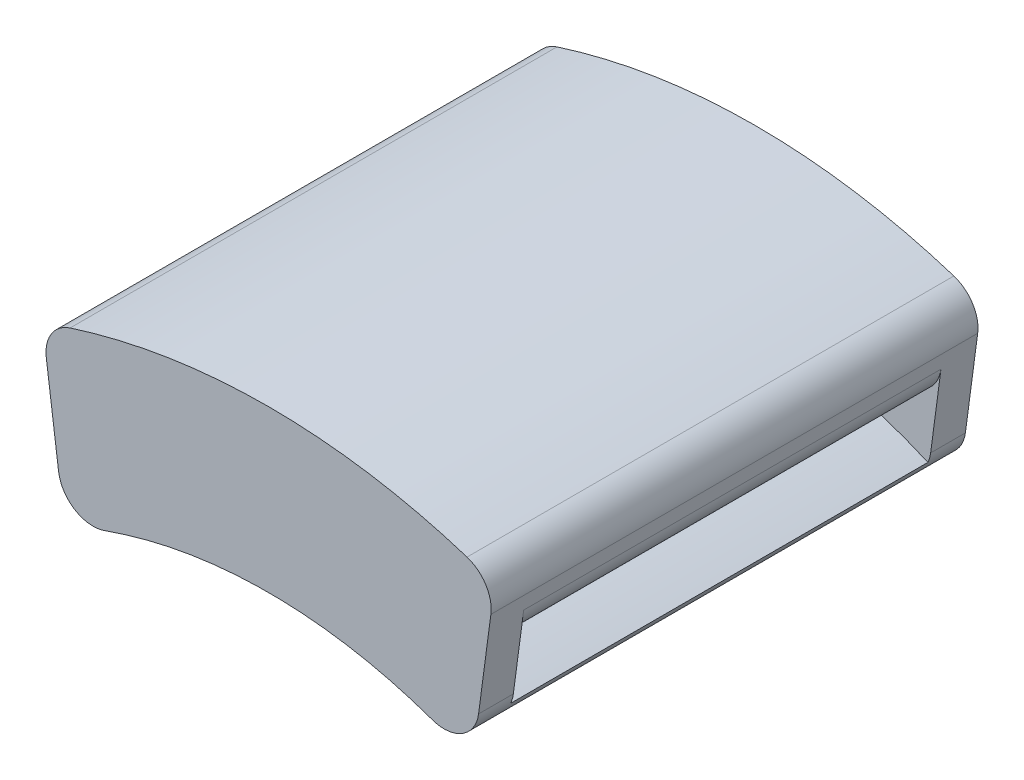
SolidWorks part; units mm, degrees
ref_plane "Front Plane" through (0, 0, 0) normal (0, 0, 1) x (1, 0, 0)
ref_plane "Top Plane" through (0, 0, 0) normal (0, 1, 0) x (1, 0, 0)
ref_plane "Right Plane" through (0, 0, 0) normal (1, 0, 0) x (0, 0, -1)
sketch "Sketch1" plane through (0, 0, 0) normal (0, 0, 1) x (1, 0, 0)
  line L0 (13.2294, 36.7301) -> (12.2963, 29.7209) construction
  line L1 (-13.2416, 36.8223) -> (-12.3085, 29.8131) construction
  line L2 (-13, 35.0072) -> (-12.3431, 30.0727)
  line L3 (13, 35.0072) -> (12.3431, 30.0727)
  line L4 (11.7361, 25.5129) -> (12, 27.4955)
  line L5 (-10, 35.0072) -> (10, 35.0072) construction
  line L6 (-10, 35.0072) -> (-10, 32.5072) construction
  line L7 (-10, 32.5072) -> (10, 32.5072) construction
  line L8 (10, 35.0072) -> (10, 32.5072) construction
  line L9 (-11.7361, 25.5129) -> (-12, 27.4955)
  circle A0 centre (0, 0) radius 30 construction
  arc A1 (-12, 27.4955) -> (12, 27.4955) centre (0, 0) cw
  arc A2 (-13, 35.0072) -> (13, 35.0072) centre (0, 0) cw
  arc A3 (-12.3431, 30.0727) -> (12.3431, 30.0727) centre (0, 0) cw
  arc A4 (-11.7361, 25.5129) -> (11.7361, 25.5129) centre (0, 0) cw
  point P7 (0, 37.3431)
  point P9 (0, 30)
  point P21 (0, 32.5072)
  dimension "D1" = 60
  dimension "D2" = 24
  dimension "D3" = 26
  dimension "D4" = 2.6
  dimension "D5" = 2
  dimension "D6" = 0
  dimension "D7" = 20
  dimension "D8" = 2.5
  dimension "D9" = 32.5072
extrude "Boss-Extrude1" add sketch "Sketch1" along normal blind 24
ref_plane "Plane1" through (0, 32.51, 0) normal (0, 1, 0) x (1, 0, 0)
sketch "Sketch4" plane through (0, 32.51, 0) normal (0, 1, 0) x (1, 0, 0)
  line L0 (0, -24) -> (0, 0) construction
  line L1 (-13, -24) -> (13, -24) construction
  line L2 (-13, -12) -> (13, -12) construction
  line L3 (-13, -24) -> (-13, 0) construction
  line L4 (13, -24) -> (13, 0) construction
  circle A0 centre (0, -12) radius 10
extrude "Cut-Extrude1" cut sketch "Sketch4" along normal blind 2.5 and the other way up to next
sketch "Sketch9" plane through (0, 32.51, 0) normal (0, 1, 0) x (1, 0, 0)
  circle A0 centre (0, -12) radius 7.5
  point P0 (0, -12)
  dimension "D1" = 15
sketch "Sketch7" plane through (0, 0, 0) normal (0, 0, -1) x (-1, 0, 0)
  line L0 (-13, 35.0072) -> (-11.7361, 25.5129)
  line L1 (13, 35.0072) -> (11.7361, 25.5129)
  arc A0 (11.7361, 25.5129) -> (-11.7361, 25.5129) centre (0, 0) ccw construction
  arc A1 (13, 35.0072) -> (-13, 35.0072) centre (0, 0) ccw construction
  arc A2 (11.7361, 25.5129) -> (-11.7361, 25.5129) centre (0, 0) ccw
  arc A3 (13, 35.0072) -> (-13, 35.0072) centre (0, 0) ccw
extrude "Boss-Extrude4" add sketch "Sketch7" along normal blind 2
sketch "Sketch8" plane through (0, 0, 24) normal (0, 0, 1) x (1, 0, 0)
  line L0 (-13, 35.0072) -> (-11.7361, 25.5129)
  line L1 (11.7361, 25.5129) -> (13, 35.0072)
  arc A0 (11.7361, 25.5129) -> (-11.7361, 25.5129) centre (0, 0) ccw construction
  arc A1 (13, 35.0072) -> (-13, 35.0072) centre (0, 0) ccw construction
  arc A2 (11.7361, 25.5129) -> (-11.7361, 25.5129) centre (0, 0) ccw
  arc A3 (13, 35.0072) -> (-13, 35.0072) centre (0, 0) ccw
extrude "Boss-Extrude5" add sketch "Sketch8" along normal blind 2
fillet "Fillet2" radius 2 6 edges at (12.3431, 30.0727, 12) (-12.3431, 30.0727, 12) (-13, 35.0072, 12) (-11.7361, 25.5129, 12) (11.7361, 25.5129, 12) (13, 35.0072, 12)
extrude "Cut-Extrude2" cut sketch "Sketch9" against normal through all
fillet "Fillet3" radius 2 1 edges at (-1.4314, 28.0463, 4.6379)
